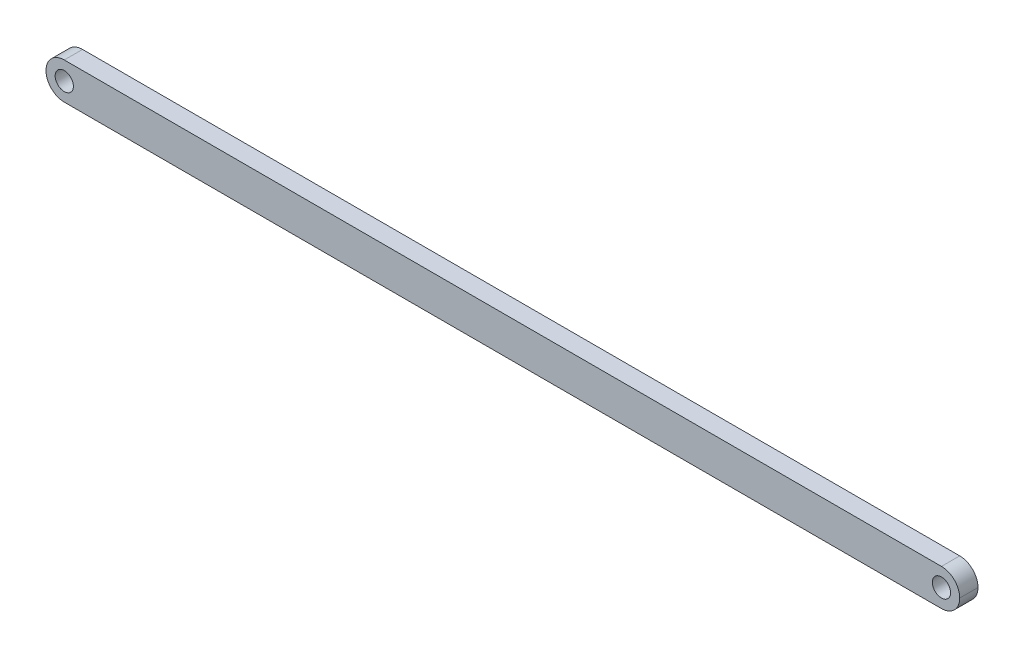
SolidWorks part; units mm, degrees
ref_plane "Front Plane" through (0, 0, 0) normal (0, 0, 1) x (1, 0, 0)
ref_plane "Top Plane" through (0, 0, 0) normal (0, 1, 0) x (1, 0, 0)
ref_plane "Right Plane" through (0, 0, 0) normal (1, 0, 0) x (0, 0, -1)
sketch "Sketch1" plane through (0, 0, 0) normal (0, 0, 1) x (1, 0, 0)
  line L1 (-250, 10) -> (250, 10)
  line L2 (-250, 10) -> (-250, -10)
  line L3 (-250, -10) -> (250, -10)
  line L4 (250, 10) -> (250, -10)
  line L5 (-250, 10) -> (250, -10) construction
  line L6 (-250, -10) -> (250, 10) construction
  circle A0 centre (-240, 0) radius 5
  circle A1 centre (240, 0) radius 5
  point P0 (0, 0)
  dimension "D4" = 10
  dimension "D5" = 10
  dimension "D6" = 10
  dimension "D1" = 500
  dimension "D2" = 20
  dimension "D3" = 10
extrude "Boss-Extrude1" add sketch "Sketch1" along normal blind 10
fillet "Fillet1" radius 10 4 edges at (250, -10, 5) (250, 10, 5) (-250, -10, 5) (-250, 10, 5)
